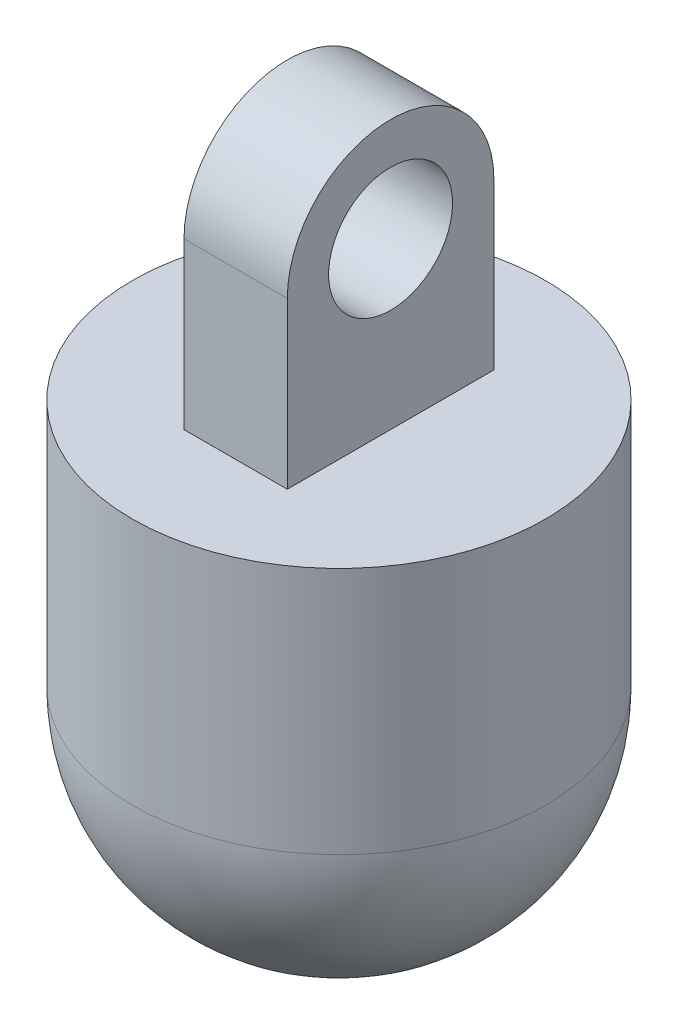
SolidWorks part; units mm, degrees
material "AISI 1020"
ref_plane "Front Plane" through (0, 0, 0) normal (0, 0, 1) x (1, 0, 0)
ref_plane "Top Plane" through (0, 0, 0) normal (0, 1, 0) x (1, 0, 0)
ref_plane "Right Plane" through (0, 0, 0) normal (1, 0, 0) x (0, 0, -1)
sketch "Sketch1" plane through (0, 0, 0) normal (0, 1, 0) x (1, 0, 0)
  circle A0 centre (0, 0) radius 50
  dimension "D1" = 100
extrude "Boss-Extrude1" add sketch "Sketch1" along normal blind 60
sketch "Sketch2" plane through (0, 0, 0) normal (1, 0, 0) x (0, 0, -1)
  line L0 (-25, 100) -> (-25, 60)
  line L1 (50, 60) -> (-50, 60) construction
  line L2 (-25, 60) -> (25, 60)
  line L3 (25, 60) -> (25, 100)
  line L4 (0, 0) -> (0, 100) construction
  arc A0 (25, 100) -> (-25, 100) centre (0, 100) ccw
  circle A1 centre (0, 100) radius 15
  dimension "D1" = 30
  dimension "D2" = 50
  dimension "D3" = 40
extrude "Boss-Extrude2" add sketch "Sketch2" along normal mid plane 25
dome "Dome1" faces to dome 1 distance 50 reverse direction no elliptical dome no face at (0, 0, 50) parameters "D1"=50
equation "\"A\"= 100"
equation "\"B\"= 100"
equation "\"C\"= 100"
equation "\"D\"= 100"
equation "\"E\"= 100"
